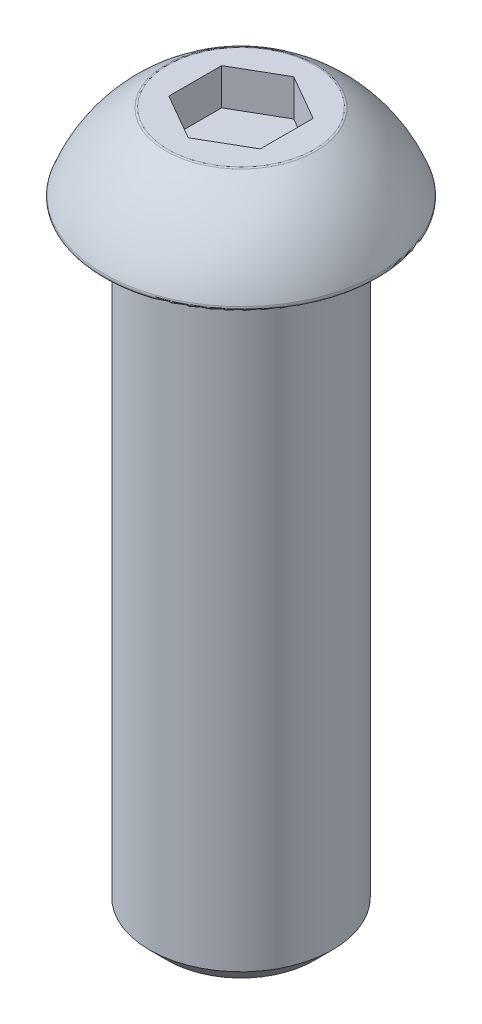
SolidWorks part; units mm, degrees
material "AISI 304"
ref_plane "前基準面" through (0, 0, 0) normal (0, 0, 1) x (1, 0, 0)
ref_plane "上基準面" through (0, 0, 0) normal (0, 1, 0) x (1, 0, 0)
ref_plane "右基準面" through (0, 0, 0) normal (1, 0, 0) x (0, 0, -1)
sketch "草圖4" plane through (0, 0, 0) normal (0, 1, 0) x (1, 0, 0)
  circle A0 centre (0, 0) radius 2.5
  dimension "D1" = 5
extrude "填料-伸長4" add sketch "草圖4" against normal blind 17
cosmetic thread "裝飾螺紋線1" parameters "D1"=8, "D2"=3
cosmetic thread "裝飾螺紋線2" [suppressed] parameters "D1"=15, "D2"=3
chamfer "導角2" distance 0.5 angle 45 1 edges at (0, -17, 2.5)
sketch "草圖2" plane through (0, 0, 0) normal (0, 1, 0) x (1, 0, 0)
  circle A0 centre (0, 0) radius 3.5
  dimension "D1" = 7
extrude "填料-伸長2" [suppressed] add sketch "草圖2" along normal blind 2.8
sketch "草圖3" [suppressed] plane through (0, 2.8, 0) normal (0, 1, 0) x (1, 0, 0)
  line L0 (0, 1.7321) -> (0, 0) construction
  line L1 (0, 1.7321) -> (-1.5, 0.866)
  line L2 (-1.5, 0.866) -> (-1.5, -0.866)
  line L3 (-1.5, -0.866) -> (0, -1.7321)
  line L4 (0, -1.7321) -> (1.5, -0.866)
  line L5 (1.5, -0.866) -> (1.5, 0.866)
  line L6 (1.5, 0.866) -> (0, 1.7321)
  circle A0 centre (0, 0) radius 1.5 construction
  dimension "D1" = 3
extrude "除料-伸長1" [suppressed] cut sketch "草圖3" against normal blind 2
chamfer "導角1" [suppressed] distance 0.5 angle 45
sketch "草圖6" plane through (0, 0, 0) normal (0, 0, 1) x (1, 0, 0)
  line L0 (0, 0) -> (0, 2.3) construction
  line L1 (3.6593, 0) -> (0, 0)
  line L2 (0, 2.2) -> (1.9985, 2.2)
  line L3 (0, 0) -> (0, 2.2)
  arc A0 (2.0498, 2.1859) -> (3.7531, 0.1346) centre (0, -1.249) cw
  arc A1 (3.7531, 0.1346) -> (3.6593, 0) centre (3.6593, 0.1) cw
  arc A2 (2.0498, 2.1859) -> (1.9985, 2.2) centre (1.9985, 2.1) ccw
  point P7 (3.8, 0)
  point P12 (2.0259, 2.2)
  dimension "D3" = 0.1
  dimension "D5" = 4
  dimension "D6" = 0.1
  dimension "D1" = 7.6
  dimension "D2" = 2.3
  dimension "D4" = 2.2
revolve "旋轉1" add sketch "草圖6" angle 360 about L0
sketch "草圖7" plane through (0, 2.2, 0) normal (0, 1, 0) x (1, 0, 0)
  line L0 (0, 0) -> (0, 1.4434) construction
  line L1 (1.25, 0.7217) -> (0, 1.4434)
  line L2 (0, 1.4434) -> (-1.25, 0.7217)
  line L3 (-1.25, 0.7217) -> (-1.25, -0.7217)
  line L4 (-1.25, -0.7217) -> (0, -1.4434)
  line L5 (0, -1.4434) -> (1.25, -0.7217)
  line L6 (1.25, -0.7217) -> (1.25, 0.7217)
  circle A0 centre (0, 0) radius 1.25 construction
  dimension "D1" = 2.5
extrude "除料-伸長2" cut sketch "草圖7" against normal blind 1
chamfer "導角3" [suppressed] distance 0.5 angle 45
sketch "草圖8" [suppressed] plane through (0, 0, 0) normal (0, 1, 0) x (1, 0, 0)
  line L0 (0, 0) -> (0, 1.4434) construction
  line L1 (0, -1.4434) -> (1.25, -0.7217)
  line L2 (1.25, -0.7217) -> (1.25, 0.7217)
  line L3 (1.25, 0.7217) -> (0, 1.4434)
  line L4 (0, 1.4434) -> (-1.25, 0.7217)
  line L5 (-1.25, 0.7217) -> (-1.25, -0.7217)
  line L6 (-1.25, -0.7217) -> (0, -1.4434)
  circle A0 centre (0, 0) radius 1.25 construction
  dimension "D1" = 2.5
extrude "除料-伸長3" [suppressed] cut sketch "草圖8" against normal blind 2
sketch "草圖9" [suppressed] plane through (0, 0, 0) normal (0, 1, 0) x (1, 0, 0)
  line L0 (0, 0) -> (0, 7.5056) construction
  line L1 (0, 7.5056) -> (-6.5, 3.7528)
  line L2 (-6.5, 3.7528) -> (-6.5, -3.7528)
  line L3 (-6.5, -3.7528) -> (0, -7.5056)
  line L4 (0, -7.5056) -> (6.5, -3.7528)
  line L5 (6.5, -3.7528) -> (6.5, 3.7528)
  line L6 (6.5, 3.7528) -> (0, 7.5056)
  circle A0 centre (0, 0) radius 6.5 construction
  dimension "D1" = 7
extrude "填料-伸長5" [suppressed] add sketch "草圖9" along normal blind 2.8
sketch "草圖11" [suppressed] plane through (0, 5.5, 0) normal (0, 1, 0) x (1, 0, 0)
  line L0 (0, 0) -> (0, 13.0049) construction
